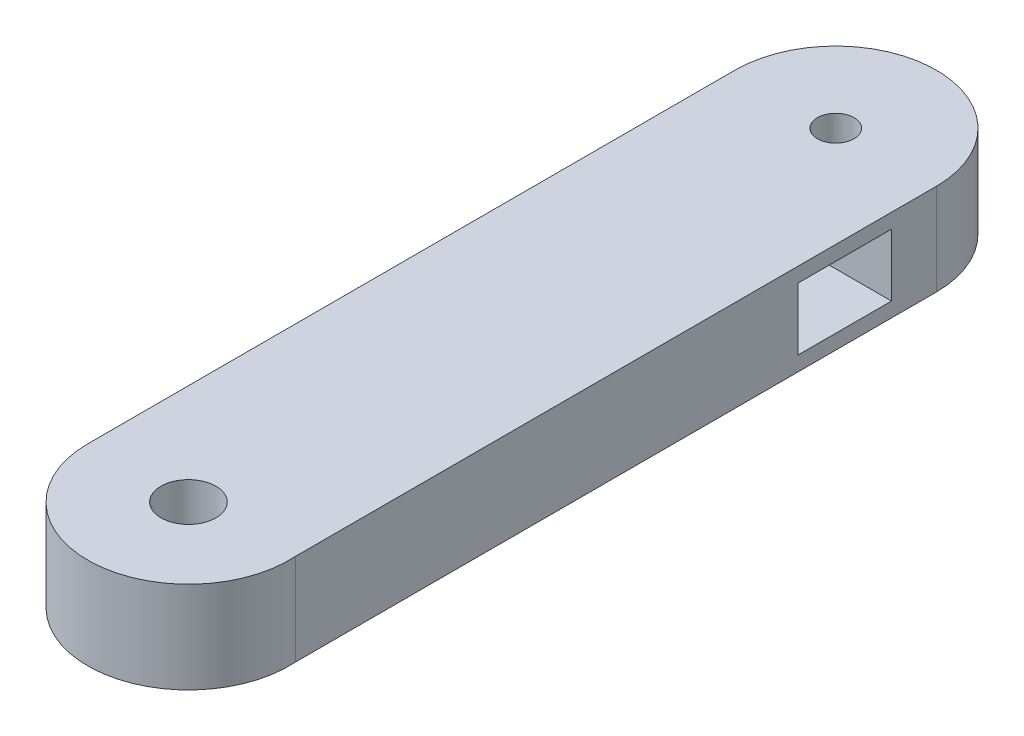
SolidWorks part; units mm, degrees
ref_plane "前视基准面" through (0, 0, 0) normal (0, 0, 1) x (1, 0, 0)
ref_plane "上视基准面" through (0, 0, 0) normal (0, 1, 0) x (1, 0, 0)
ref_plane "右视基准面" through (0, 0, 0) normal (1, 0, 0) x (0, 0, -1)
other "Configuration Table"
sketch "草图1" plane through (0, 0, 0) normal (0, 0, 1) x (1, 0, 0)
  line L0 (0, 0) -> (0, 48.7698) construction
  line L1 (-2.4, 0) -> (-5.5, 0)
  line L2 (-5.5, 0) -> (-5.5, 5)
  line L3 (-5.5, 5) -> (-4.25, 5)
  line L6 (-1.5, 3.8) -> (-1.5, 2.66)
  line L9 (-4.25, 5) -> (-1.5, 5)
  line L10 (-1.5, 5) -> (-1.5, 3.8)
  line L11 (-1.5, 2.66) -> (-1.5, 0)
  line L12 (-1.5, 0) -> (-2.4, 0)
  dimension "D1" = 5
  dimension "D2" = 5.5
  dimension "D7" = 3
revolve "旋转1" add sketch "草图1" angle 360 about L0
ref_plane "基准面1" through (0, 2, 0) normal (0, -1, 0) x (-1, 0, 0)
sketch "草图2" plane through (0, 2, 0) normal (0, -1, 0) x (-1, 0, 0)
  line L2 (-5.4892, 0.3437) -> (-5.4892, 35.3438)
  line L5 (5.5, 0) -> (5.5, 35.3438)
  circle A1 centre (0, 0) radius 5.5 construction
  arc A2 (5.5, 0) -> (-5.4892, 0.3437) centre (0, 0) ccw
  circle A4 centre (0, 0) radius 5.5 construction
  arc A5 (5.5, 35.3438) -> (-5.4892, 35.3438) centre (0.0054, 35.3438) ccw
  dimension "D1" = 35
  dimension "D2" = 35.3438
  dimension "D3" = 5.4946
extrude "凸台-拉伸1" add sketch "草图2" against normal up to surface (3 mm away) up to face at (0, 5, -5.5)
sketch "草图4" plane through (0, 2, 0) normal (0, -1, 0) x (1, 0, 0)
  line L0 (-5.5, -35.3438) -> (5.4892, -35.3437) construction
  circle A2 centre (-0.0054, -35.3438) radius 1
  arc A3 (-5.5, -35.3438) -> (5.4892, -35.3438) centre (-0.0054, -35.3438) ccw construction
  dimension "D1" = 2
extrude "切除-拉伸1" cut sketch "草图4" against normal mid plane 10
extrude "凸台-拉伸3" add sketch "草图2<2>" along normal up to surface (2 mm away) up to face at (0, 0, -1.5)
sketch "草图2<2>" plane through (0, 2, 0) normal (0, -1, 0) x (-1, 0, 0) same geometry as "草图2"
extrude "切除-拉伸2" cut sketch "草图4<2>" along normal blind 10
sketch "草图4<2>" plane through (0, 2, 0) normal (0, -1, 0) x (1, 0, 0) same geometry as "草图4"
sketch "草图6" plane through (5.4892, 0, 0) normal (1, 0, 0) x (0, 0, -1)
  line L0 (0.3437, 5) -> (4.5318, 5) construction
  line L1 (0.3437, 5) -> (35.3438, 5) construction
  line L2 (3.3437, 5) -> (3.3437, 2.5) construction
  line L3 (35.3438, 2.5) -> (30.3438, 2.5) construction
  line L8 (35.3438, 5) -> (35.3438, 0) construction
  line L11 (32.8937, 4.2) -> (27.7937, 4.2)
  line L12 (32.8937, 4.2) -> (32.8937, 0.8)
  line L13 (32.8937, 0.8) -> (27.7937, 0.8)
  line L14 (27.7937, 4.2) -> (27.7937, 0.8)
  line L15 (32.8937, 4.2) -> (27.7937, 0.8) construction
  line L16 (32.8937, 0.8) -> (27.7937, 4.2) construction
  dimension "D3" = 5
  dimension "D1" = 3
  dimension "D2" = 2.5
  dimension "D4" = 3.4
  dimension "D5" = 5.1
  dimension "D6" = 2.5
extrude "切除-拉伸3" cut sketch "草图6" against normal through all
